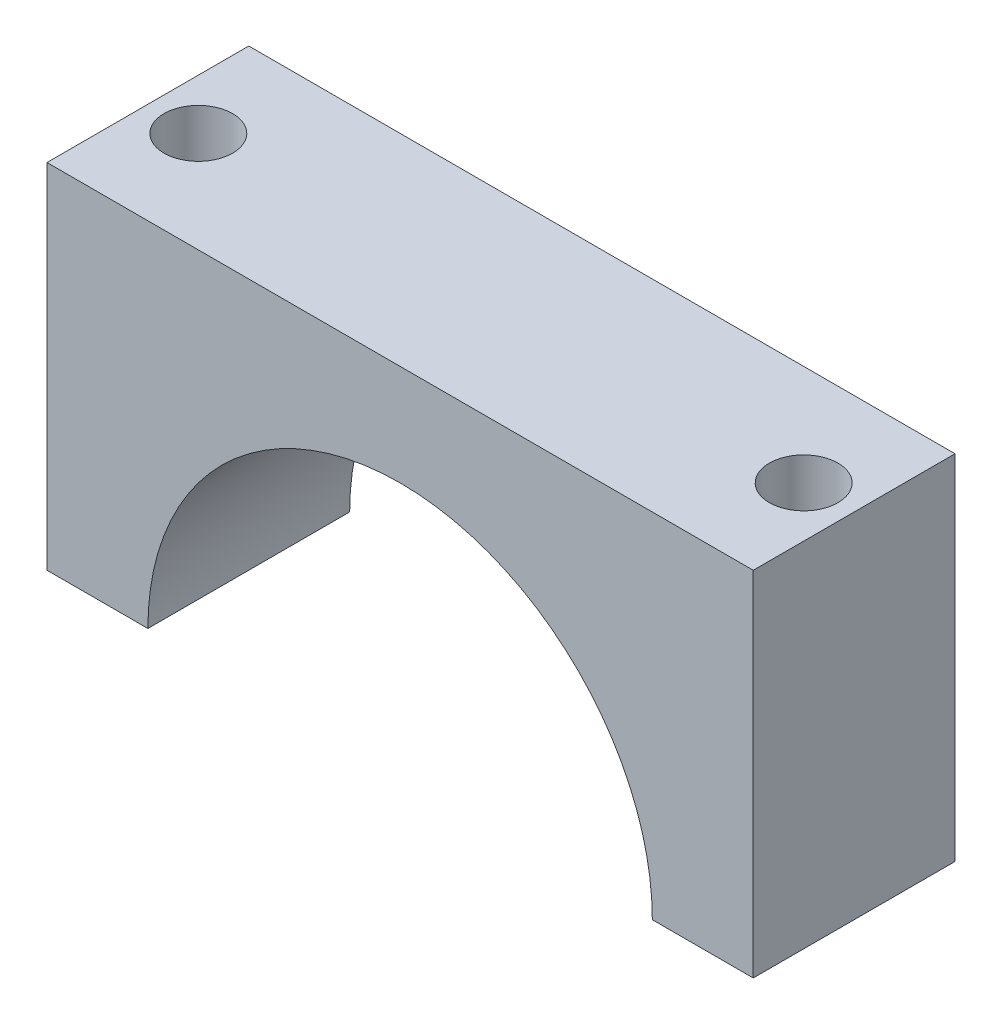
SolidWorks part; units mm, degrees
material "6061 Alloy"
ref_plane "Front Plane" through (0, 0, 0) normal (0, 0, 1) x (1, 0, 0)
ref_plane "Top Plane" through (0, 0, 0) normal (0, 1, 0) x (1, 0, 0)
ref_plane "Right Plane" through (0, 0, 0) normal (1, 0, 0) x (0, 0, -1)
sketch "Sketch2" plane through (0, 0, 0) normal (0, 0, 1) x (1, 0, 0)
  line L0 (12.5, 0) -> (17.5, 0)
  line L2 (-17.5, 0) -> (-17.5, 17.5)
  line L3 (-17.5, 17.5) -> (17.5, 17.5)
  line L4 (17.5, 0) -> (17.5, 17.5)
  line L7 (-12.5, 0) -> (-17.5, 0)
  arc A0 (12.5, 0) -> (-12.5, 0) centre (0, 0) ccw
  dimension "D1" = 12.5
  dimension "D2" = 17.5
  dimension "D3" = 35
  dimension "D4" = 17.5
extrude "Boss-Extrude1" add sketch "Sketch2" along normal blind 10
hole_wizard "M3 Clearance Hole1" positions "Sketch5" profile "Sketch4" hole size "M3" standard "ANSI Metric" end condition through all
sketch "Sketch5" plane through (0, 17.5, 0) normal (0, 1, 0) x (1, 0, 0)
  line L1 (17.5, -10) -> (-17.5, -10) construction
  line L5 (-17.5, -10) -> (-17.5, 0) construction
  line L6 (17.5, -10) -> (17.5, 0) construction
  point P0 (-15, -5)
  point P2 (15, -5)
  dimension "D1" = 2.5
  dimension "D2" = 5
  dimension "D3" = 5
  dimension "D4" = 2.5
sketch "Sketch4" plane through (-15, 17.5, 5) normal (1, 0, 0) x (0, 0, 1)
  line L0 (0, 0) -> (0, 17.5)
  line L1 (0, 17.5) -> (1.7, 17.5)
  line L2 (1.7, 17.5) -> (1.7, 0)
  line L5 (1.7, 0) -> (0, 0)
  line L11 (0, -6.35) -> (0, 107.95) construction
  dimension "Thru Hole Dia." = 3.4
  dimension "Thru Hole Depth" = 17.5
